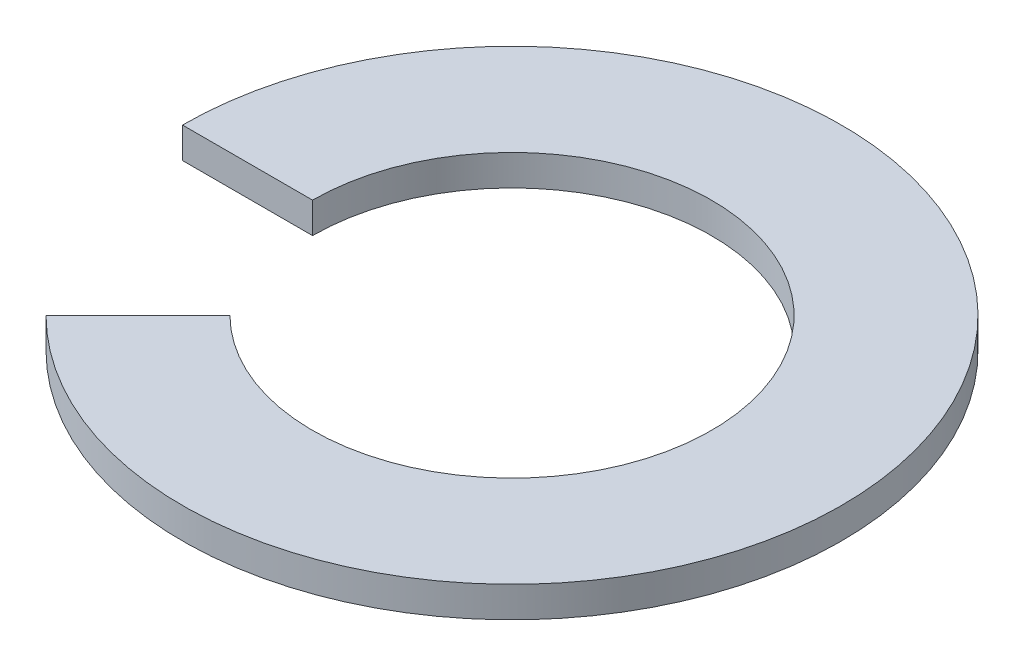
SolidWorks part; units mm, degrees
ref_plane "Front Plane" through (0, 0, 0) normal (0, 0, 1) x (1, 0, 0)
ref_plane "Top Plane" through (0, 0, 0) normal (0, 1, 0) x (1, 0, 0)
ref_plane "Right Plane" through (0, 0, 0) normal (1, 0, 0) x (0, 0, -1)
sketch "Sketch1" plane through (0, 0, 0) normal (0, 1, 0) x (1, 0, 0)
  line L0 (0, 0) -> (-16.0655, 0)
  line L1 (0, 0) -> (-11.36, -11.36)
  arc A0 (-6.8766, -6.8766) -> (-9.725, 0) centre (0, 0) ccw
  arc A1 (-11.36, -11.36) -> (-16.0655, 0) centre (0, 0) ccw
  dimension "D1" = 19.45
  dimension "D2" = 32.131
  dimension "D3" = 45
extrude "Boss-Extrude1" add sketch "Sketch1" along normal blind 1.5 contours L1 A1 L0 A0 region at (-12.8953, 0, -0.4544)
